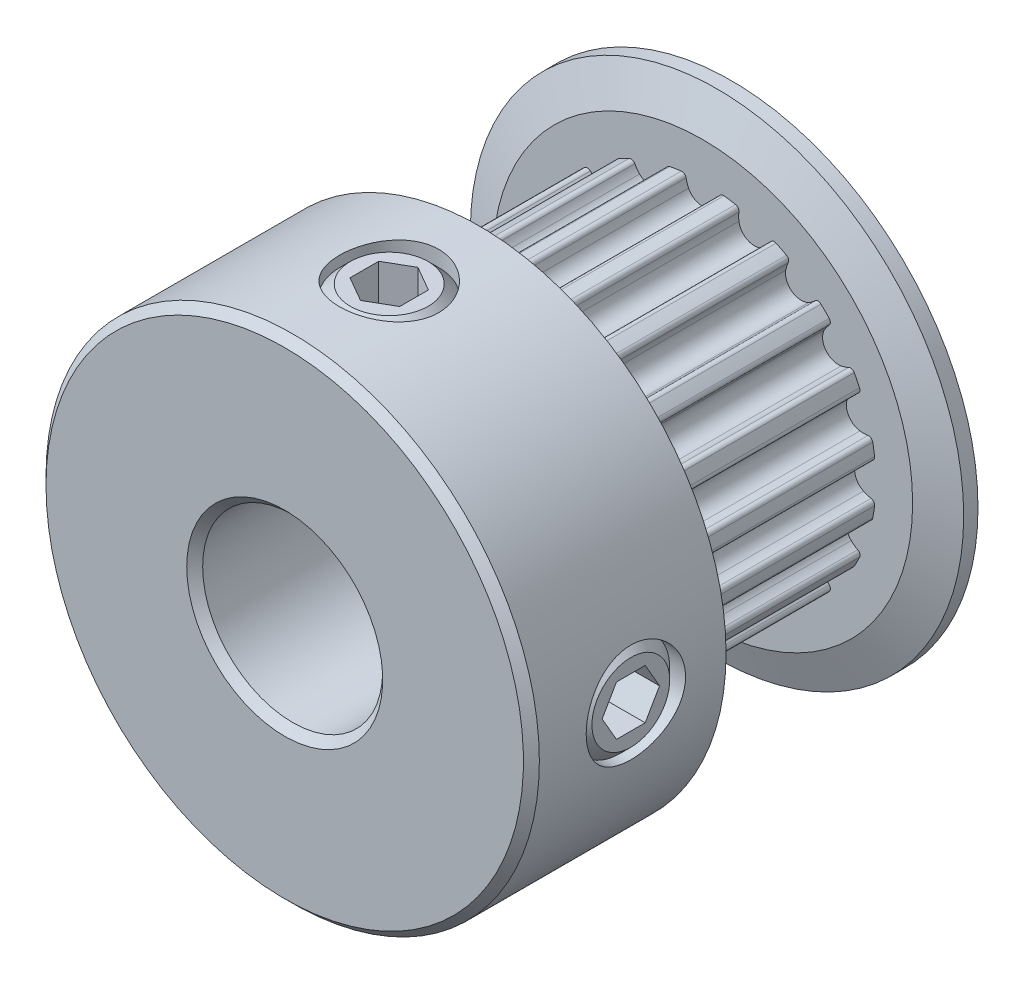
SolidWorks part; units mm, degrees
ref_plane "Front Plane" through (0, 0, 0) normal (0, 0, 1) x (1, 0, 0)
ref_plane "Top Plane" through (0, 0, 0) normal (0, 1, 0) x (1, 0, 0)
ref_plane "Right Plane" through (0, 0, 0) normal (1, 0, 0) x (0, 0, -1)
sketch "Sketch1" plane through (0, 0, 0) normal (0, 0, 1) x (1, 0, 0)
  line L1 (-1.7499, 5.3585) -> (1.7499, 5.3585) construction
  line L4 (0, 0) -> (0, 5.3585) construction
  line L5 (0, 5.3585) -> (0, 11.1847) construction
  line L6 (0, 6.3625) -> (1.9751, 6.0482) construction
  line L7 (1.9751, 6.0482) -> (2.6648, 5.8229) construction
  line L8 (1.9751, 6.0482) -> (1.7499, 5.3585) construction
  line L9 (-1.9751, 6.0482) -> (-1.7499, 5.3585) construction
  line L10 (-1.8963, 5.8067) -> (-2.841, 8.6995)
  line L11 (-2.841, 8.6995) -> (2.841, 8.6995)
  line L12 (2.841, 8.6995) -> (1.8963, 5.8067)
  circle A0 centre (0, 0) radius 6.3625 construction
  circle A1 centre (0, 0) radius 8.6995 construction
  circle A2 centre (0, 0) radius 6.1085 construction
  arc A3 (-0.4989, 5.6703) -> (0.4989, 5.6703) centre (0, 5.9135) ccw
  arc A4 (-0.4989, 5.6703) -> (-0.5855, 5.9387) centre (0.4, 6.1085) cw
  arc A5 (-1.8963, 5.8067) -> (-0.7518, 6.0621) centre (0, 0) cw
  arc A6 (-0.5855, 5.9387) -> (-0.7518, 6.0621) centre (-0.7333, 5.9132) ccw
  arc A7 (1.8963, 5.8067) -> (0.7518, 6.0621) centre (0, 0) ccw
  arc A8 (0.5855, 5.9387) -> (0.7518, 6.0621) centre (0.7333, 5.9132) cw
  arc A9 (0.4989, 5.6703) -> (0.5855, 5.9387) centre (-0.4, 6.1085) ccw
  point P6 (0, 20.9083)
  point P11 (0, 6.3625)
  point P13 (0, 8.6995)
  point P14 (0, 6.1085)
  dimension "D1" = 9.7237
  dimension "D2" = 4.8222
sketch "Sketch2" plane through (0, 0, 0) normal (1, 0, 0) x (0, 0, -1)
  line L0 (-7.875, 3.175) -> (7.875, 3.175)
  line L1 (-7.875, 3.175) -> (-7.875, 8.6995)
  line L2 (-1.01, 8.6995) -> (-7.875, 8.6995)
  line L3 (-1.515, 3.175) -> (-1.515, 8.6995) construction
  line L4 (-1.515, 8.6995) -> (-0.505, 8.6995) construction
  line L5 (-0.505, 8.6995) -> (-0.505, 6.1085) construction
  line L6 (-0.505, 6.1085) -> (6.865, 6.1085)
  line L7 (6.865, 6.1085) -> (6.865, 8.6995) construction
  line L8 (6.865, 8.6995) -> (7.875, 8.6995) construction
  line L9 (7.875, 8.6995) -> (7.875, 3.175)
  line L10 (-7.875, 0) -> (7.875, 0) construction
  line L11 (7.37, 8.6995) -> (6.865, 7.404)
  line L12 (-0.505, 7.404) -> (-1.01, 8.6995)
  line L14 (-0.505, 7.404) -> (-0.505, 6.1085)
  line L15 (6.865, 6.1085) -> (6.865, 7.404)
  line L16 (7.37, 8.6995) -> (7.875, 8.6995)
  arc A0 (-0.505, 7.404) -> (-1.01, 8.6995) centre (-2.4192, 7.404) ccw construction
  arc A1 (6.865, 7.404) -> (7.37, 8.6995) centre (8.7792, 7.404) cw construction
  point P12 (-0.505, 7.404)
  point P14 (-1.01, 8.6995)
  point P20 (6.865, 7.404)
  point P21 (7.37, 8.6995)
  point P25 (6.865, 0)
  point P26 (-0.505, 0)
  dimension "OA" = 15.75
  dimension "Bore" = 6.35
  dimension "Outside Width" = 8.38
  dimension "Inside Width" = 7.37
revolve "Revolve1" add sketch "Sketch2" angle 360 mid plane about L10
sketch "Sketch3" plane through (0, 0, 0) normal (0, 0, 1) x (1, 0, 0)
  line L6 (2.841, 8.6995) -> (-2.841, 8.6995)
  line L7 (1.8963, 5.8067) -> (2.841, 8.6995)
  line L8 (-2.841, 8.6995) -> (-1.8963, 5.8067)
  line L9 (2.841, 8.6995) -> (-2.841, 8.6995)
  line L10 (1.8963, 5.8067) -> (2.841, 8.6995)
  line L11 (-2.841, 8.6995) -> (-1.8963, 5.8067)
  arc A8 (1.8963, 5.8067) -> (0.7518, 6.0621) centre (0, 0) ccw
  arc A9 (0.7518, 6.0621) -> (0.5855, 5.9387) centre (0.7333, 5.9132) ccw
  arc A10 (0.4989, 5.6703) -> (0.5855, 5.9387) centre (-0.4, 6.1085) ccw
  arc A11 (-0.4989, 5.6703) -> (0.4989, 5.6703) centre (0, 5.9135) ccw
  arc A12 (-0.5855, 5.9387) -> (-0.4989, 5.6703) centre (0.4, 6.1085) ccw
  arc A13 (-0.5855, 5.9387) -> (-0.7518, 6.0621) centre (-0.7333, 5.9132) ccw
  arc A14 (-0.7518, 6.0621) -> (-1.8963, 5.8067) centre (0, 0) ccw
  arc A15 (1.8963, 5.8067) -> (0.7518, 6.0621) centre (0, 0) ccw
  arc A16 (0.7518, 6.0621) -> (0.5855, 5.9387) centre (0.7333, 5.9132) ccw
  arc A17 (0.4989, 5.6703) -> (0.5855, 5.9387) centre (-0.4, 6.1085) ccw
  arc A18 (-0.4989, 5.6703) -> (0.4989, 5.6703) centre (0, 5.9135) ccw
  arc A19 (-0.5855, 5.9387) -> (-0.4989, 5.6703) centre (0.4, 6.1085) ccw
  arc A20 (-0.5855, 5.9387) -> (-0.7518, 6.0621) centre (-0.7333, 5.9132) ccw
  arc A21 (-0.7518, 6.0621) -> (-1.8963, 5.8067) centre (0, 0) ccw
  dimension "D1" = 0
extrude "Cut-Extrude1" cut sketch "Sketch3" against normal up to vertex (6.865 mm away) from vertex up to point (0, 6.1085, -6.865) starting at point (0, 6.1085, 0.505)
pattern_circular "CirPattern1" count 20 over 360 about axis through (0, 0, 7.875) along (0, 0, 1) of "Cut-Extrude1"
sketch "Sketch4" plane through (0, 0, 0) normal (1, 0, 0) x (0, -1, 0)
  line L0 (0, -0.505) -> (0, -7.875) construction
  line L1 (-3.175, -7.875) -> (3.175, -7.875) construction
  line L2 (7.404, -0.505) -> (-7.404, -0.505) construction
  circle A0 centre (0, -4.19) radius 1.7526
extrude "Cut-Extrude2" cut sketch "Sketch4" along normal through all
ref_plane "Plane1" through (0, 0, 4.19) normal (0, 0, 1) x (1, 0, 0)
sketch "Sketch5" plane through (0, 0, 4.19) normal (0, 0, 1) x (1, 0, 0)
  line L0 (0, 0) -> (0, 8.6995) construction
  line L1 (3.175, -1.3716) -> (3.175, 0)
  line L2 (3.556, -1.7526) -> (8.1401, -1.7526)
  line L3 (3.175, 0) -> (8.6995, 0) construction
  line L4 (3.175, 0) -> (8.5211, 0)
  line L5 (8.5211, 0) -> (8.5211, -1.3716)
  line L6 (3.556, -1.7526) -> (3.175, -1.3716)
  line L7 (8.5211, -1.3716) -> (8.1401, -1.7526)
  circle A0 centre (0, 0) radius 8.6995 construction
  circle A1 centre (0, 0) radius 3.175 construction
  point P2 (3.175, -1.7526)
  point P11 (8.5211, -1.7526)
revolve "Revolve2" add sketch "Sketch5" angle 360 mid plane about L4
sketch "Sketch6" plane through (8.5211, 5.3841, 0) normal (-1, 0, 0) x (0, -1, 0)
  line L1 (5.3841, 5.2019) -> (4.5078, 4.6959)
  line L2 (4.5078, 4.6959) -> (4.5078, 3.6841)
  line L3 (4.5078, 3.6841) -> (5.3841, 3.1781)
  line L4 (5.3841, 3.1781) -> (6.2604, 3.6841)
  line L5 (6.2604, 3.6841) -> (6.2604, 4.6959)
  line L6 (6.2604, 4.6959) -> (5.3841, 5.2019)
  circle A0 centre (5.3841, 4.19) radius 0.8763 construction
  dimension "D1" = 1.7526
extrude "Cut-Extrude3" cut sketch "Sketch6" along normal blind 1.3144
pattern_circular "CirPattern3" count 2 over 90 about axis through (0, 0, 7.875) along (0, 0, 1) of "Cut-Extrude2", "Revolve2", "Cut-Extrude3"
chamfer "Chamfer1" distance 0.2807 angle 45 2 edges at (3.175, 0, 7.875) (8.6995, 0, 7.875)
ref_axis "Center Axis 1" through (0, 0, -7.875) along (0, 0, 1)
ref_plane "Contact Plane 1" through (0, 0, 7.875) normal (0, 0, 1) x (1, 0, 0)
ref_plane "Contact Plane 2" through (0, 0, -7.875) normal (0, 0, -1) x (-1, 0, 0)
equation "\"D2@Sketch1\"= \"D1@Sketch1\" / 2"
equation "\"D1@Sketch6\" = \"Set Screw@Sketch4\" / 2"
equation "\"D1@Cut-Extrude3\" = \"D1@Sketch6\"*.75"
